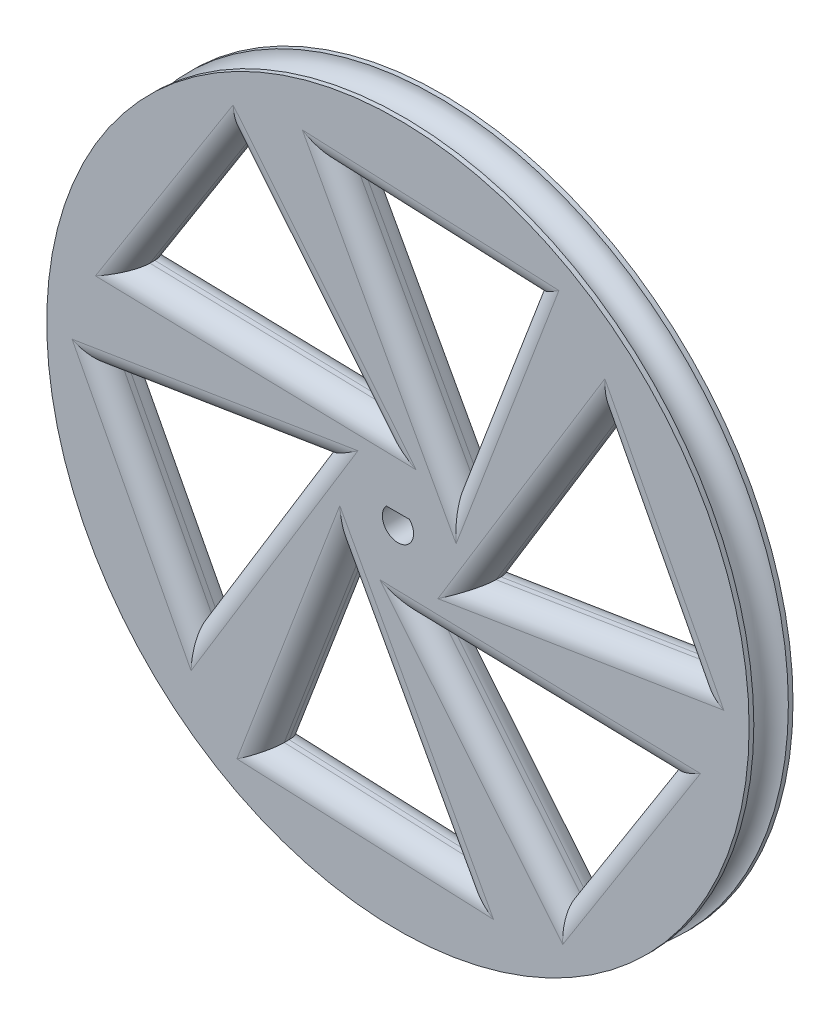
SolidWorks part; units mm, degrees
ref_plane "Front Plane" through (0, 0, 0) normal (0, 0, 1) x (1, 0, 0)
ref_plane "Top Plane" through (0, 0, 0) normal (0, 1, 0) x (1, 0, 0)
ref_plane "Right Plane" through (0, 0, 0) normal (1, 0, 0) x (0, 0, -1)
sketch "Sketch4" plane through (0, 0, 0) normal (1, 0, 0) x (0, 0, -1)
  line L0 (4.02, 36) -> (4.5, 36)
  line L1 (0, 0) -> (4.5, 0)
  line L2 (0, 0) -> (0, 36)
  line L3 (0, 36) -> (0.48, 36)
  line L4 (4.5, 0) -> (4.5, 36)
  arc A0 (0.48, 36) -> (4.02, 36) centre (2.25, 36) ccw
  dimension "D3" = 3.54
  dimension "D1" = 4.5
  dimension "D2" = 36
revolve "Revolve1" add sketch "Sketch4" angle 360 about L1
sketch "Sketch5" plane through (0, 0, 0) normal (0, 0, 1) x (1, 0, 0)
  line L3 (-1.1926, 1.0667) -> (1.1926, 1.0667)
  arc A0 (-1.1926, 1.0667) -> (1.1926, 1.0667) centre (0, 0) ccw
  dimension "D1" = 3.2
extrude "Cut-Extrude2" cut sketch "Sketch5" against normal blind 5
sketch "Sketch6" plane through (0, 0, 0) normal (0, 0, 1) x (1, 0, 0)
  line L0 (5.633, 6.059) -> (-6.35, 28)
  line L1 (-6.35, 28) -> (13.65, 27.1605)
  line L2 (13.65, 27.1605) -> (5.633, 6.059)
  circle A0 centre (0, 0) radius 36 construction
  dimension "D1" = 25
  dimension "D2" = 28
  dimension "D3" = 20
extrude "Cut-Extrude3" cut sketch "Sketch6" against normal blind 5
pattern_circular "CirPattern2" count 6 every 60 about axis through (0, 0, 0) along (0, 0, 1) of "Cut-Extrude3"
fillet "Fillet10" radius 2 1 edges at (-0.3585, 17.0295, 0)
fillet "Fillet11" radius 2 1 edges at (-9.5637, 16.6547, 0)
fillet "Fillet12" radius 2 1 edges at (-21.4954, 17.8409, 0)
fillet "Fillet13" radius 2 1 edges at (-14.7782, 8.2008, 0)
fillet "Fillet14" radius 2 1 edges at (9.1741, 15.3794, 0)
fillet "Fillet15" radius 2 1 edges at (14.5687, 8.8252, 0)
fillet "Fillet16" radius 2 1 edges at (17.9059, -0.2553, 0)
fillet "Fillet17" radius 2 1 edges at (3.5368, 27.585, 0)
fillet "Fillet18" radius 2 1 edges at (25.6577, 10.7295, 0)
fillet "Fillet19" radius 2 1 edges at (14.9272, -8.2043, 0)
fillet "Fillet20" radius 2 1 edges at (8.7319, -15.6346, 0)
fillet "Fillet21" radius 2 8 edges at (-25.7102, -10.6291, -4.5) (-25.7102, -10.6291, 0) (-19.2052, 0.0449, 0) (-14.5687, -8.8252, -4.5) (-9.6415, -16.6097, 0) (-3.65, -27.5803, 0) (0.3585, -17.0295, -4.5) (22.1209, -16.8555, 0)
fillet "Fillet22" radius 2 1 edges at (0.2871, -16.8987, 0)
fillet "Fillet23" radius 2 1 edges at (-14.4912, -8.698, 0)
fillet "Fillet24" radius 2 15 edges at (-2.4839, -27.6292, -4.5) (-9.1741, -15.3794, -4.5) (-18.9463, 0.0869, -4.5) (-14.9272, 8.2043, -4.5) (-22.0602, 16.9512, -4.5) (-9.5637, 16.6547, -4.5) (-0.3585, 17.0295, -4.5) (3.65, 27.5803, -4.5) (9.6415, 16.6097, -4.5) (14.5687, 8.8252, -4.5) (25.7102, 10.6291, -4.5) (19.2052, -0.0449, -4.5) (9.5637, -16.6547, -4.5) (14.9272, -8.2043, -4.5) (22.0602, -16.9512, -4.5)
